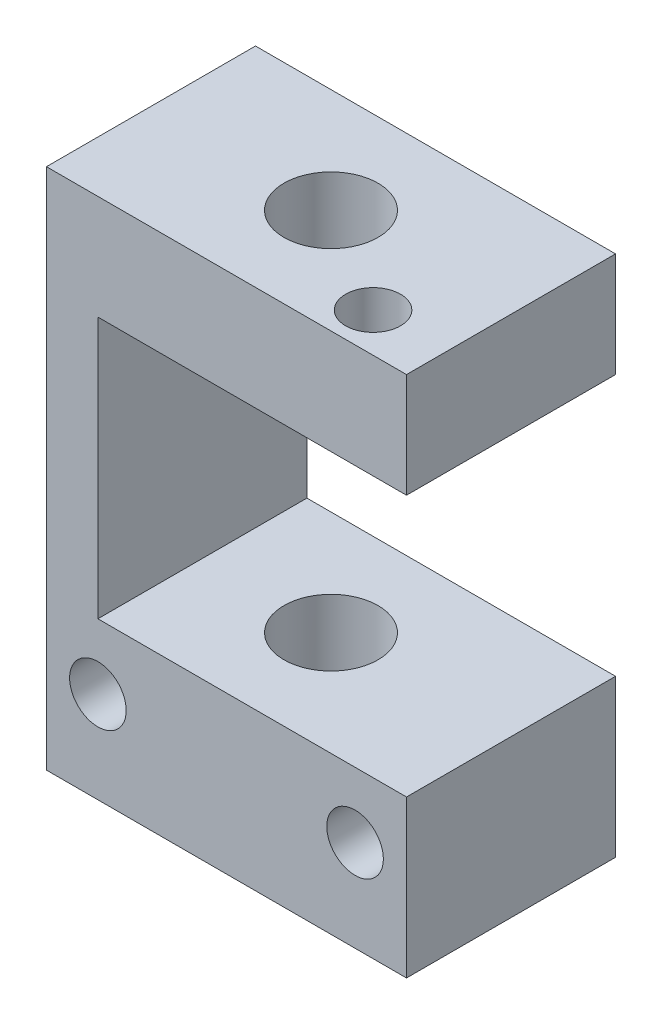
SolidWorks part; units mm, degrees
ref_plane "Front Plane" through (0, 0, 0) normal (0, 0, 1) x (1, 0, 0)
ref_plane "Top Plane" through (0, 0, 0) normal (0, 1, 0) x (1, 0, 0)
ref_plane "Right Plane" through (0, 0, 0) normal (1, 0, 0) x (0, 0, -1)
sketch "Sketch2" plane through (0, 0, 0) normal (0, 1, 0) x (1, 0, 0)
  line L1 (0, 0) -> (35, 0)
  line L2 (0, 0) -> (0, 20.32)
  line L3 (0, 20.32) -> (35, 20.32)
  line L4 (35, 0) -> (35, 20.32)
  circle A0 centre (17.5, 10.16) radius 4.572
  point P8 (17.5, 20.32)
  point P9 (0, 10.16)
  dimension "D3" = 9.144
  dimension "D1" = 35
  dimension "D2" = 20.32
extrude "Boss-Extrude1" add sketch "Sketch2" along normal blind 50.8
hole_wizard "M5 Clearance Hole1" positions "Sketch3" profile "Sketch4" hole size "M5" standard "ANSI Metric" end condition through all
sketch "Sketch3" plane through (0, 0, 0) normal (0, 0, 1) x (1, 0, 0)
  line L0 (5, 8.89) -> (30, 8.89) construction
  line L2 (0, 0) -> (35, 0) construction
  point P0 (5, 8.89)
  point P2 (30, 8.89)
  point P9 (17.5, 0)
  point P10 (17.5, 8.89)
  dimension "D1" = 25
  dimension "D2" = 8.89
sketch "Sketch4" plane through (5, 8.89, 0) normal (1, 0, 0) x (0, -1, 0)
  line L0 (0, 0) -> (0, 20.32)
  line L1 (0, 20.32) -> (2.75, 20.32)
  line L2 (2.75, 20.32) -> (2.75, 0)
  line L5 (2.75, 0) -> (0, 0)
  line L11 (0, -6.35) -> (0, 107.95) construction
  dimension "Thru Hole Dia." = 5.5
  dimension "Thru Hole Depth" = 20.32
sketch "Sketch7" plane through (0, 50.8, 0) normal (0, 1, 0) x (1, 0, 0)
  line L0 (0, 0) -> (35, 0) construction
  circle A0 centre (27.94, 3.81) radius 2.667
  point P5 (27.0814, 2.3495)
  dimension "D3" = 5.334
  dimension "D1" = 27.94
  dimension "D2" = 3.81
extrude "Cut-Extrude1" cut sketch "Sketch7" against normal blind 5
sketch "Sketch8" plane through (0, 0, -20.32) normal (0, 0, -1) x (-1, 0, 0)
  line L0 (-35, 50.8) -> (-35, 0) construction
  line L1 (-35, 40.64) -> (-5, 40.64)
  line L2 (-35, 40.64) -> (-35, 15.24)
  line L3 (-35, 15.24) -> (-5, 15.24)
  line L4 (-5, 40.64) -> (-5, 15.24)
  line L6 (0, 50.8) -> (0, 0) construction
  circle A0 centre (-30, 8.89) radius 2.75 construction
  dimension "D2" = 6.35
  dimension "D1" = 25.4
  dimension "D3" = 5
extrude "Cut-Extrude2" cut sketch "Sketch8" against normal through all
equation "\"press fit\"= 0.3mm"
equation "\"pin diamiter\"= 5mm"
equation "\"D3@Sketch7\"=\"pin diamiter\"+\"press fit\""
equation "\"marker diamiter + a little\"= 0.35in"
equation "\"D3@Sketch2\"=\"marker diamiter + a little\"+\"press fit\""
